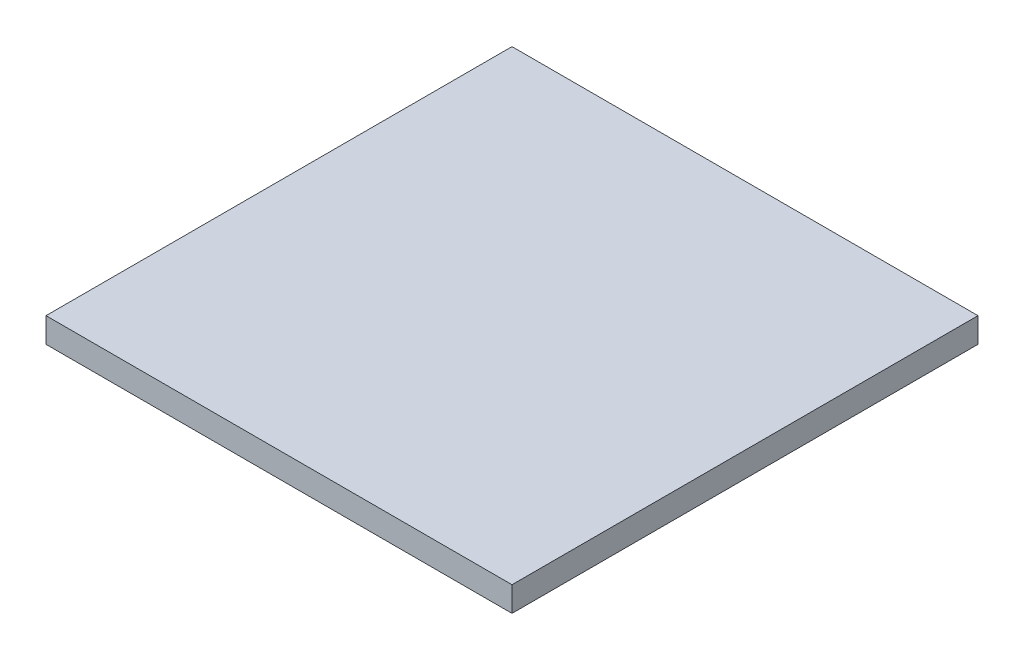
SolidWorks part; units mm, degrees
material "AISI 1020"
ref_plane "Спереди" through (0, 0, 0) normal (0, 0, 1) x (1, 0, 0)
ref_plane "Сверху" through (0, 0, 0) normal (0, 1, 0) x (1, 0, 0)
ref_plane "Справа" through (0, 0, 0) normal (1, 0, 0) x (0, 0, -1)
sketch "Эскиз1" plane through (0, 0, 0) normal (0, 1, 0) x (1, 0, 0)
  line L1 (-75, 75) -> (75, 75)
  line L2 (-75, 75) -> (-75, -75)
  line L3 (-75, -75) -> (75, -75)
  line L4 (75, 75) -> (75, -75)
  line L5 (-75, 75) -> (75, -75) construction
  line L6 (-75, -75) -> (75, 75) construction
  point P0 (0, 0)
  dimension "D1" = 150
base flange "Базовая кромка1" sketch "Эскиз1" thickness 8 reverse thickness direction no parameters "D1"=0.75
sketch "Сгиб-Линии1" [suppressed] plane through (0, 0, 0) normal (0, 1, 0) x (1, 0, 0)
sketch "Граничная рамка1" [suppressed] plane through (0, 0, 0) normal (0, 1, 0) x (1, 0, 0)
sheet metal parameters "Листовой металл3" thickness 8 parameters "D1"=0.75
flat pattern "Развертка3" [suppressed]
sketch "Сгиб-Линии2" plane through (0, 0, 0) normal (0, 1, 0) x (1, 0, 0)
sketch3d "Граничная рамка2" [suppressed]
  line L0 (75, -75, 0) -> (-75, -75, 0) construction
  line L1 (75, 75, 0) -> (-75, 75, 0) construction
  line L2 (75, -75, 0) -> (75, 75, 0) construction
  line L3 (-75, -75, 0) -> (-75, 75, 0) construction
